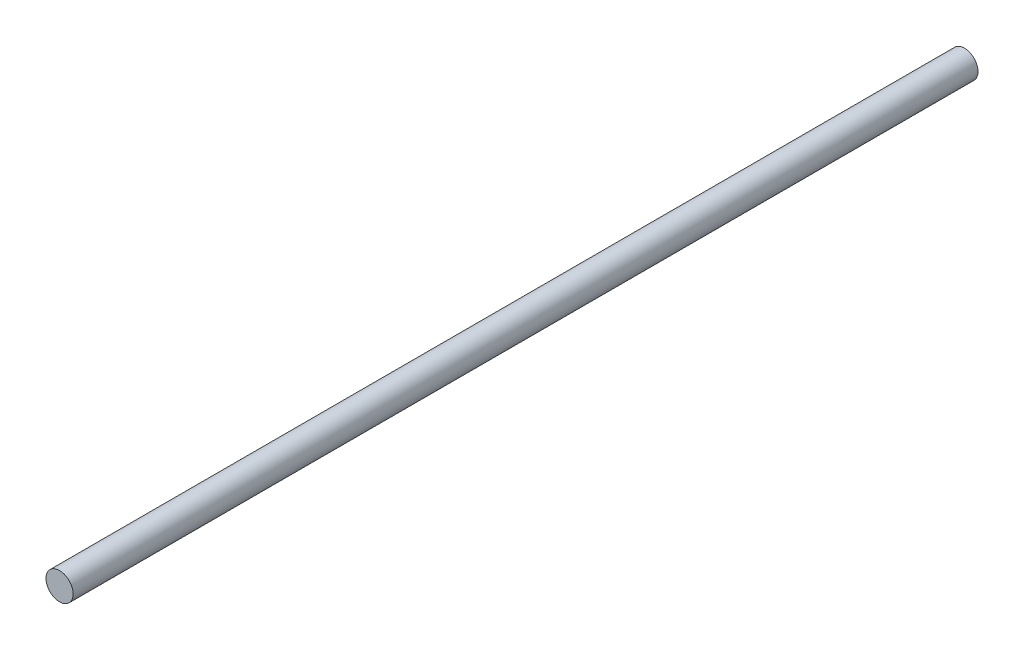
SolidWorks part; units mm, degrees
ref_plane "前视基准面" through (0, 0, 0) normal (0, 0, 1) x (1, 0, 0)
ref_plane "上视基准面" through (0, 0, 0) normal (0, 1, 0) x (1, 0, 0)
ref_plane "右视基准面" through (0, 0, 0) normal (1, 0, 0) x (0, 0, -1)
sketch "草图1" plane through (0, 0, 0) normal (0, 0, 1) x (1, 0, 0)
  circle A0 centre (0, 0) radius 1.5
extrude "凸台-拉伸1" add sketch "草图1" along normal blind 100
ref_axis "基准轴1" through (0, 0, 100) along (0, 0, -1)
ref_axis "基准轴2" through (0, 0, 100) along (0, 0, -1)
